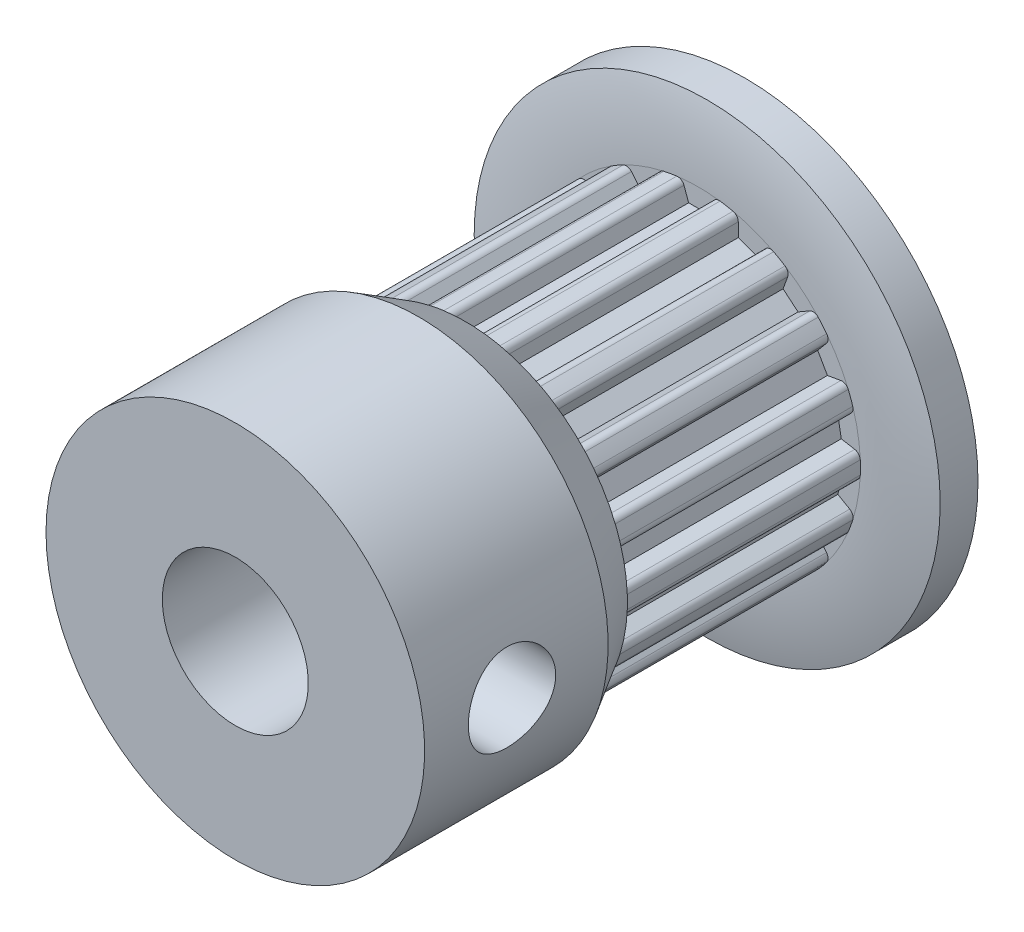
SolidWorks part; units mm, degrees
material "ABS"
ref_plane "Front Plane" through (0, 0, 0) normal (0, 0, 1) x (1, 0, 0)
ref_plane "Top Plane" through (0, 0, 0) normal (0, 1, 0) x (1, 0, 0)
ref_plane "Right Plane" through (0, 0, 0) normal (1, 0, 0) x (0, 0, -1)
sketch "Sketch8" plane through (0, 0, 0) normal (1, 0, 0) x (0, 0, -1)
  line L0 (7.5979, 0) -> (-14.162, 0) construction
  line L1 (5.6, -2.5063) -> (5.6, -8)
  line L2 (4, -5.5625) -> (-4, -5.5625)
  line L3 (-5.6, -6.5) -> (-4, -5.5625)
  line L4 (5.6, -8) -> (4.3016, -8)
  line L10 (-5.6, -6.5) -> (-11.9, -6.5)
  line L12 (-11.9, -6.5) -> (-11.9, -2.5063)
  line L13 (5.6, -2.5063) -> (-11.9, -2.5063)
  arc A0 (4.3016, -8) -> (4, -5.5625) centre (14, -5.5625) cw
  dimension "D1" = 2.5063
revolve "Revolve1" add sketch "Sketch8" angle 360 about L0
sketch "Sketch7" plane through (0, 0, 0) normal (0, 0, 1) x (1, 0, 0)
  line L0 (-1.9984, 4.5111) -> (-1.3688, 4.7402)
  line L4 (-1.3688, 4.7402) -> (-1.3688, 5.2095)
  line L5 (-1.9984, 4.5111) -> (-2.3, 4.8705)
  line L7 (-0.335, 4.9225) -> (0.335, 4.9225)
  line L9 (0.335, 4.9225) -> (0.4955, 5.3635)
  line L11 (-0.335, 4.9225) -> (-0.4955, 5.3635)
  line L12 (1.3688, 4.7402) -> (1.9984, 4.5111)
  line L13 (1.9984, 4.5111) -> (2.3, 4.8705)
  line L14 (1.3688, 4.7402) -> (1.3688, 5.2095)
  line L15 (2.9075, 3.9862) -> (3.4207, 3.5555)
  line L16 (3.4207, 3.5555) -> (3.8271, 3.7902)
  line L17 (2.9075, 3.9862) -> (3.068, 4.4272)
  line L18 (4.0955, 2.7514) -> (4.4305, 2.1711)
  line L19 (4.4305, 2.1711) -> (4.8926, 2.2526)
  line L20 (4.0955, 2.7514) -> (4.3971, 3.1108)
  line L21 (4.7895, 1.1847) -> (4.9059, 0.5249)
  line L22 (4.9059, 0.5249) -> (5.368, 0.4434)
  line L23 (4.7895, 1.1847) -> (5.1959, 1.4193)
  line L24 (4.9059, -0.5249) -> (4.7895, -1.1847)
  line L25 (4.7895, -1.1847) -> (5.1959, -1.4193)
  line L26 (4.9059, -0.5249) -> (5.368, -0.4434)
  line L27 (4.4305, -2.1711) -> (4.0955, -2.7514)
  line L28 (4.0955, -2.7514) -> (4.3971, -3.1108)
  line L29 (4.4305, -2.1711) -> (4.8926, -2.2526)
  line L30 (3.4207, -3.5555) -> (2.9075, -3.9862)
  line L31 (2.9075, -3.9862) -> (3.068, -4.4272)
  line L32 (3.4207, -3.5555) -> (3.8271, -3.7902)
  line L33 (1.9984, -4.5111) -> (1.3688, -4.7402)
  line L34 (1.3688, -4.7402) -> (1.3688, -5.2095)
  line L35 (1.9984, -4.5111) -> (2.3, -4.8705)
  line L36 (0.335, -4.9225) -> (-0.335, -4.9225)
  line L37 (-0.335, -4.9225) -> (-0.4955, -5.3635)
  line L38 (0.335, -4.9225) -> (0.4955, -5.3635)
  line L39 (-1.3688, -4.7402) -> (-1.9984, -4.5111)
  line L40 (-1.9984, -4.5111) -> (-2.3, -4.8705)
  line L41 (-1.3688, -4.7402) -> (-1.3688, -5.2095)
  line L42 (-2.9075, -3.9862) -> (-3.4207, -3.5555)
  line L43 (-3.4207, -3.5555) -> (-3.8271, -3.7902)
  line L44 (-2.9075, -3.9862) -> (-3.068, -4.4272)
  line L45 (-4.0955, -2.7514) -> (-4.4305, -2.1711)
  line L46 (-4.4305, -2.1711) -> (-4.8926, -2.2526)
  line L47 (-4.0955, -2.7514) -> (-4.3971, -3.1108)
  line L48 (-4.7895, -1.1847) -> (-4.9059, -0.5249)
  line L49 (-4.9059, -0.5249) -> (-5.368, -0.4434)
  line L50 (-4.7895, -1.1847) -> (-5.1959, -1.4193)
  line L51 (-4.9059, 0.5249) -> (-4.7895, 1.1847)
  line L52 (-4.7895, 1.1847) -> (-5.1959, 1.4193)
  line L53 (-4.9059, 0.5249) -> (-5.368, 0.4434)
  line L54 (-4.4305, 2.1711) -> (-4.0955, 2.7514)
  line L55 (-4.0955, 2.7514) -> (-4.3971, 3.1108)
  line L56 (-4.4305, 2.1711) -> (-4.8926, 2.2526)
  line L57 (-3.4207, 3.5555) -> (-2.9075, 3.9862)
  line L58 (-2.9075, 3.9862) -> (-3.068, 4.4272)
  line L59 (-3.4207, 3.5555) -> (-3.8271, 3.7902)
  arc A0 (0.7423, 5.5127) -> (0.4955, 5.3635) centre (0.7116, 5.2848) ccw
  arc A2 (-1.1879, 5.4342) -> (-1.3688, 5.2095) centre (-1.1388, 5.2095) ccw
  arc A3 (-2.3, 4.8705) -> (-2.583, 4.9264) centre (-2.4762, 4.7227) ccw
  arc A4 (-0.4955, 5.3635) -> (-0.7423, 5.5127) centre (-0.7116, 5.2848) ccw
  arc A6 (0.7423, 5.5127) -> (-0.7423, 5.5127) centre (0, 0) ccw
  arc A7 (2.583, 4.9264) -> (2.3, 4.8705) centre (2.4762, 4.7227) ccw
  arc A8 (-1.1879, 5.4342) -> (-2.583, 4.9264) centre (0, 0) ccw
  arc A9 (1.3688, 5.2095) -> (1.1879, 5.4342) centre (1.1388, 5.2095) ccw
  arc A10 (2.583, 4.9264) -> (1.1879, 5.4342) centre (0, 0) ccw
  arc A11 (4.1122, 3.7459) -> (3.8271, 3.7902) centre (3.9421, 3.591) ccw
  arc A12 (3.068, 4.4272) -> (2.9749, 4.7002) centre (2.8519, 4.5058) ccw
  arc A13 (4.1122, 3.7459) -> (2.9749, 4.7002) centre (0, 0) ccw
  arc A14 (5.1453, 2.1135) -> (4.8926, 2.2526) centre (4.9326, 2.0261) ccw
  arc A15 (4.3971, 3.1108) -> (4.403, 3.3992) centre (4.221, 3.2587) ccw
  arc A16 (5.1453, 2.1135) -> (4.403, 3.3992) centre (0, 0) ccw
  arc A17 (5.5579, 0.2262) -> (5.368, 0.4434) centre (5.3281, 0.2169) ccw
  arc A18 (5.1959, 1.4193) -> (5.3001, 1.6883) centre (5.0809, 1.6185) ccw
  arc A19 (5.5579, 0.2262) -> (5.3001, 1.6883) centre (0, 0) ccw
  arc A20 (5.3001, -1.6883) -> (5.1959, -1.4193) centre (5.0809, -1.6185) ccw
  arc A21 (5.368, -0.4434) -> (5.5579, -0.2262) centre (5.3281, -0.2169) ccw
  arc A22 (5.3001, -1.6883) -> (5.5579, -0.2262) centre (0, 0) ccw
  arc A23 (4.403, -3.3992) -> (4.3971, -3.1108) centre (4.221, -3.2587) ccw
  arc A24 (4.8926, -2.2526) -> (5.1453, -2.1135) centre (4.9326, -2.0261) ccw
  arc A25 (4.403, -3.3992) -> (5.1453, -2.1135) centre (0, 0) ccw
  arc A26 (2.9749, -4.7002) -> (3.068, -4.4272) centre (2.8519, -4.5058) ccw
  arc A27 (3.8271, -3.7902) -> (4.1122, -3.7459) centre (3.9421, -3.591) ccw
  arc A28 (2.9749, -4.7002) -> (4.1122, -3.7459) centre (0, 0) ccw
  arc A29 (1.1879, -5.4342) -> (1.3688, -5.2095) centre (1.1388, -5.2095) ccw
  arc A30 (2.3, -4.8705) -> (2.583, -4.9264) centre (2.4762, -4.7227) ccw
  arc A31 (1.1879, -5.4342) -> (2.583, -4.9264) centre (0, 0) ccw
  arc A32 (-0.7423, -5.5127) -> (-0.4955, -5.3635) centre (-0.7116, -5.2848) ccw
  arc A33 (0.4955, -5.3635) -> (0.7423, -5.5127) centre (0.7116, -5.2848) ccw
  arc A34 (-0.7423, -5.5127) -> (0.7423, -5.5127) centre (0, 0) ccw
  arc A35 (-2.583, -4.9264) -> (-2.3, -4.8705) centre (-2.4762, -4.7227) ccw
  arc A36 (-1.3688, -5.2095) -> (-1.1879, -5.4342) centre (-1.1388, -5.2095) ccw
  arc A37 (-2.583, -4.9264) -> (-1.1879, -5.4342) centre (0, 0) ccw
  arc A38 (-4.1122, -3.7459) -> (-3.8271, -3.7902) centre (-3.9421, -3.591) ccw
  arc A39 (-3.068, -4.4272) -> (-2.9749, -4.7002) centre (-2.8519, -4.5058) ccw
  arc A40 (-4.1122, -3.7459) -> (-2.9749, -4.7002) centre (0, 0) ccw
  arc A41 (-5.1453, -2.1135) -> (-4.8926, -2.2526) centre (-4.9326, -2.0261) ccw
  arc A42 (-4.3971, -3.1108) -> (-4.403, -3.3992) centre (-4.221, -3.2587) ccw
  arc A43 (-5.1453, -2.1135) -> (-4.403, -3.3992) centre (0, 0) ccw
  arc A44 (-5.5579, -0.2262) -> (-5.368, -0.4434) centre (-5.3281, -0.2169) ccw
  arc A45 (-5.1959, -1.4193) -> (-5.3001, -1.6883) centre (-5.0809, -1.6185) ccw
  arc A46 (-5.5579, -0.2262) -> (-5.3001, -1.6883) centre (0, 0) ccw
  arc A47 (-5.3001, 1.6883) -> (-5.1959, 1.4193) centre (-5.0809, 1.6185) ccw
  arc A48 (-5.368, 0.4434) -> (-5.5579, 0.2262) centre (-5.3281, 0.2169) ccw
  arc A49 (-5.3001, 1.6883) -> (-5.5579, 0.2262) centre (0, 0) ccw
  arc A50 (-4.403, 3.3992) -> (-4.3971, 3.1108) centre (-4.221, 3.2587) ccw
  arc A51 (-4.8926, 2.2526) -> (-5.1453, 2.1135) centre (-4.9326, 2.0261) ccw
  arc A52 (-4.403, 3.3992) -> (-5.1453, 2.1135) centre (0, 0) ccw
  arc A53 (-2.9749, 4.7002) -> (-3.068, 4.4272) centre (-2.8519, 4.5058) ccw
  arc A54 (-3.8271, 3.7902) -> (-4.1122, 3.7459) centre (-3.9421, 3.591) ccw
  arc A55 (-2.9749, 4.7002) -> (-4.1122, 3.7459) centre (0, 0) ccw
  point P152 (0, 0)
  dimension "D1" = 18
extrude "Cut-Extrude1" cut sketch "Sketch7" against normal blind 4 and the other way blind 4
hole_wizard "Ø3.0 (3) Diameter Hole1" positions "3DSketch1" profile "Sketch6" hole size "Ø3.0" standard "ANSI Metric" end condition up to next
sketch3d "3DSketch1"
  point P0 (6.5, 0, 8.9)
sketch "Sketch6" plane through (6.5, 0, 8.9) normal (0, 1, 0) x (0, 0, -1)
  line L0 (0, 0) -> (0, 3.9937)
  line L1 (0, 3.9937) -> (1.5, 3.9937)
  line L2 (1.5, 3.9937) -> (1.5, 0)
  line L5 (1.5, 0) -> (0, 0)
  line L11 (0, -6.35) -> (0, 107.95) construction
  dimension "Thru Hole Dia." = 3
  dimension "Thru Hole Depth" = 3.9937
